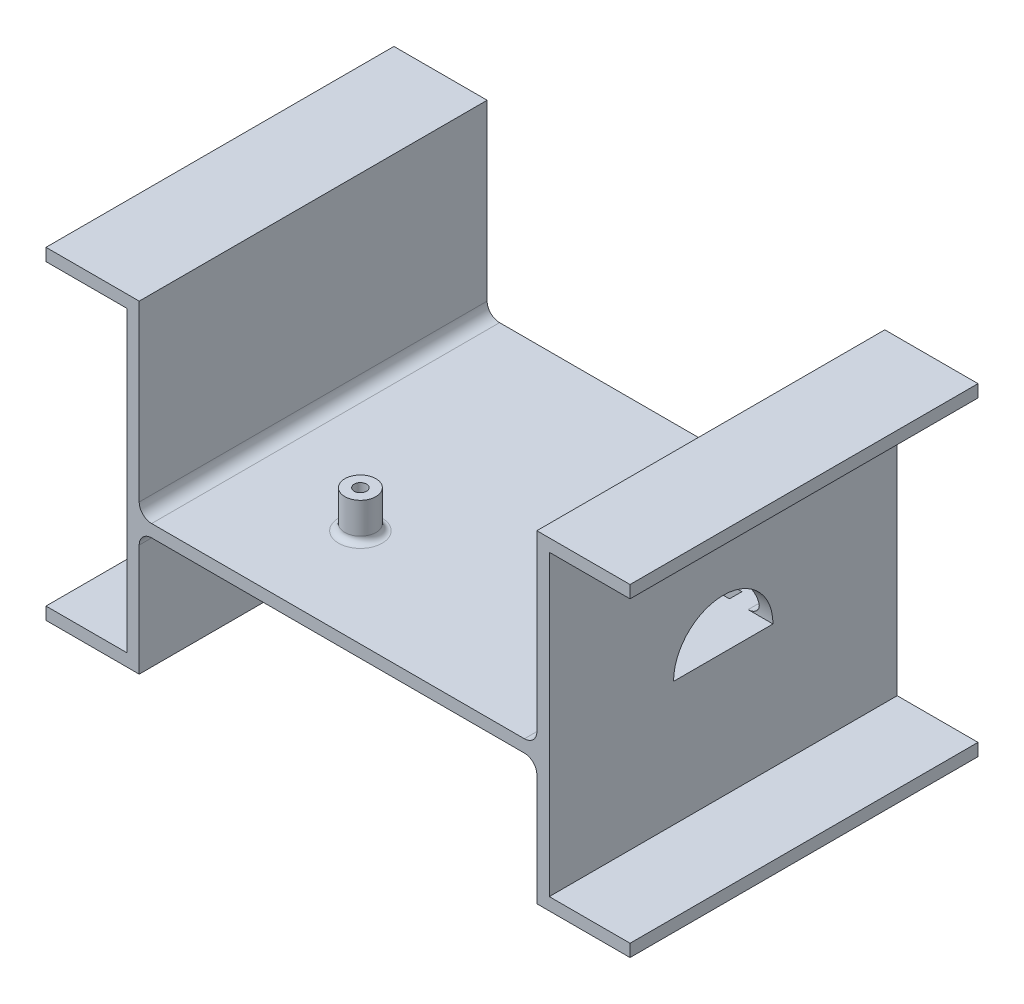
SolidWorks part; units mm, degrees
ref_plane "Front Plane" through (0, 0, 0) normal (0, 0, 1) x (1, 0, 0)
ref_plane "Top Plane" through (0, 0, 0) normal (0, 1, 0) x (1, 0, 0)
ref_plane "Right Plane" through (0, 0, 0) normal (1, 0, 0) x (0, 0, -1)
sketch "Sketch1" plane through (0, 0, 0) normal (0, 0, 1) x (1, 0, 0)
  line L0 (2, 50) -> (2, 20) construction
  line L1 (0, 0) -> (2, 0)
  line L2 (0, 0) -> (0, 48)
  line L3 (0, 48) -> (2, 48)
  line L4 (2, 0) -> (2, 48)
  line L5 (2, 48) -> (-13, 48)
  line L6 (2, 48) -> (2, 50)
  line L7 (2, 50) -> (-13, 50)
  line L8 (-13, 48) -> (-13, 50)
  line L9 (2, 0) -> (-13, 0)
  line L10 (2, 0) -> (2, -2)
  line L11 (2, -2) -> (-13, -2)
  line L12 (-13, 0) -> (-13, -2)
  line L13 (66, 20) -> (66, 48) construction
  line L14 (2, 20) -> (66, 20)
  line L15 (2, 20) -> (2, 18)
  line L16 (2, 18) -> (66, 18)
  line L17 (66, 20) -> (66, 18)
  line L19 (66, 48) -> (68, 48)
  line L20 (66, 48) -> (66, 0)
  line L21 (66, 0) -> (68, 0)
  line L22 (68, 48) -> (68, 0)
  line L23 (66, 48) -> (81, 48)
  line L24 (66, 48) -> (66, 50)
  line L25 (66, 50) -> (81, 50)
  line L26 (81, 48) -> (81, 50)
  line L27 (66, 0) -> (81, 0)
  line L28 (66, 0) -> (66, -2)
  line L29 (66, -2) -> (81, -2)
  line L30 (81, 0) -> (81, -2)
  dimension "D1" = 2
  dimension "D2" = 48
  dimension "D3" = 2
  dimension "D4" = 15
  dimension "D5" = 2
  dimension "D6" = 15
  dimension "D7" = 30
  dimension "D8" = 2
  dimension "D9" = 64
  dimension "D11" = 48
  dimension "D12" = 2
  dimension "D13" = 2
  dimension "D14" = 15
  dimension "D15" = 2
  dimension "D16" = 15
extrude "Boss-Extrude2" add sketch "Sketch1" along normal blind 56 contours L8 L5 L3 L6 L7 | L1 L4 L3 L2 | L9 L12 L11 L10 L1 | L17 L14 L4 L16 | L22 L19 L20 L17 L21 | L30 L27 L21 L28 L29 | L23 L26 L25 L24 L19 region at (1, 24, 0) region at (-5.5, -1, 0) region at (-5.5, 49, 0) region at (34, 19, 0) region at (67, 24, 0) region at (73.5, -1, 0) region at (73.5, 49, 0)
sketch "Sketch2" plane through (0, 20, 0) normal (0, 1, 0) x (1, 0, 0)
  line L0 (2, -28) -> (66, -28) construction
  line L1 (2, -56) -> (2, 0) construction
  line L2 (66, -56) -> (66, 0) construction
  line L3 (66, -28) -> (61, -28) construction
  line L4 (46.2, -15.8) -> (21.8, -15.8)
  line L5 (46.2, -15.8) -> (46.2, -40.2)
  line L6 (46.2, -40.2) -> (21.8, -40.2)
  line L7 (21.8, -15.8) -> (21.8, -40.2)
  line L8 (46.2, -15.8) -> (21.8, -40.2) construction
  line L9 (46.2, -40.2) -> (21.8, -15.8) construction
  line L10 (61, -28) -> (61, -20) construction
  line L11 (61, -28) -> (61, -36) construction
  line L12 (61, -20) -> (55, -20)
  line L13 (61, -20) -> (61, -18)
  line L14 (61, -18) -> (55, -18)
  line L15 (55, -20) -> (55, -18)
  line L17 (61, -36) -> (55, -36)
  line L18 (61, -36) -> (61, -38)
  line L19 (61, -38) -> (55, -38)
  line L20 (55, -36) -> (55, -38)
  circle A0 centre (21.8, -40.2) radius 2.5
  circle A1 centre (46.2, -15.8) radius 2.5
  circle A2 centre (21.8, -40.2) radius 1
  circle A3 centre (46.2, -15.8) radius 1
  point P6 (34, -28)
  dimension "D2" = 5
  dimension "D3" = 5
  dimension "D4" = 2
  dimension "D5" = 2
  dimension "D1" = 24.4
  dimension "D6" = 5
  dimension "D7" = 8
  dimension "D8" = 2
  dimension "D9" = 6
  dimension "D10" = 8
  dimension "D11" = 2
  dimension "D12" = 6
extrude "Boss-Extrude3" add sketch "Sketch2" along normal blind 6 contours A3 L5 A1 L4 | A3 L4 A1 L5 | A2 L7 A0 L6 | A2 L6 A0 L7 region at (45.0177, 20, 16.9823) region at (44.45, 20, 15.7293) region at (22.9823, 20, 39.0177) region at (21.7293, 20, 38.45)
sketch "Sketch3" plane through (0, 20, 0) normal (0, 1, 0) x (1, 0, 0)
  circle A0 centre (46.2, -15.8) radius 1
  circle A1 centre (21.8, -40.2) radius 1
extrude "Cut-Extrude1" cut sketch "Sketch3" against normal blind 31
extrude "Cut-Extrude2" cut sketch "Sketch2<3>" against normal blind 31 contours L15 L12 L13 L14 | L17 L20 L19 L18 region at (58, 20, 19) region at (58, 20, 37)
sketch "Sketch2<3>" plane through (0, 20, 0) normal (0, 1, 0) x (1, 0, 0) same geometry as "Sketch2"
sketch "Sketch6" plane through (66, 0, 0) normal (-1, 0, 0) x (0, 0, 1)
  line L0 (0, 20) -> (28, 20) construction
  line L1 (36, 20) -> (20, 20)
  arc A0 (20, 20) -> (36, 20) centre (28, 20) cw
  dimension "D2" = 8
  dimension "D1" = 28
extrude "Cut-Extrude3" cut sketch "Sketch6" against normal blind 31
fillet "Fillet1" radius 1 2 edges at (21.8, 20, 42.7) (46.2, 20, 18.3)
fillet "Fillet2" radius 2 5 edges at (2, 18, 28) (66, 18, 28) (2, 20, 28) (66, 20, 46) (66, 20, 10)
